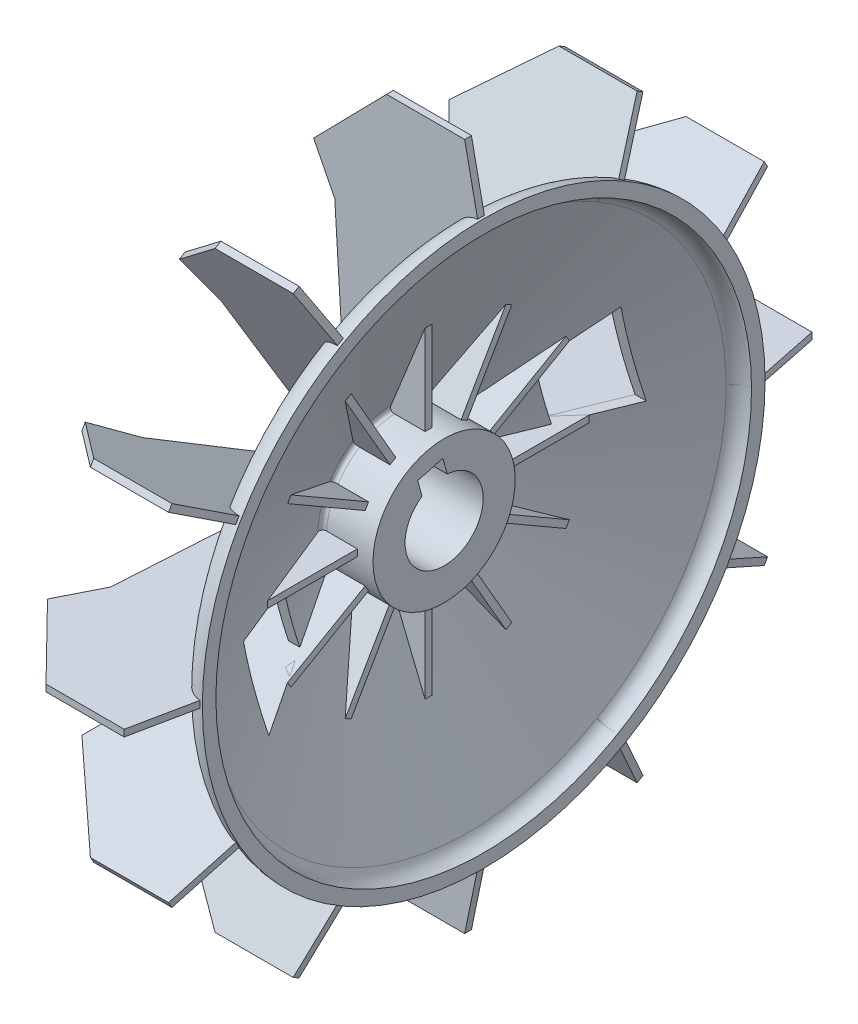
SolidWorks part; units mm, degrees
ref_plane "Plan de face" through (0, 0, 0) normal (0, 0, 1) x (1, 0, 0)
ref_plane "Plan de dessus" through (0, 0, 0) normal (0, 1, 0) x (1, 0, 0)
ref_plane "Plan de droite" through (0, 0, 0) normal (1, 0, 0) x (0, 0, -1)
sketch "Esquisse1" plane through (0, 0, 0) normal (0, 0, 1) x (1, 0, 0)
  line L0 (-19.7316, 0) -> (54.854, 0) construction
  line L1 (0, 7.5) -> (0, 13.65)
  line L2 (0, 13.65) -> (6.1585, 13.65)
  line L3 (20, 13.65) -> (20, 7.5)
  line L4 (20, 7.5) -> (0, 7.5)
  line L5 (8.4746, 15.209) -> (22.9677, 50.882)
  line L6 (27.6, 54) -> (27.6, 51.4)
  line L7 (10.4194, 14.6823) -> (24.5808, 49.5388)
  line L8 (11.1142, 13.65) -> (20, 13.65)
  arc A0 (22.9677, 50.882) -> (27.6, 54) centre (27.6, 49) cw
  arc A1 (24.5808, 49.5388) -> (27.6, 51.4) centre (27.3601, 48.4096) cw
  arc A2 (6.1585, 13.65) -> (8.4746, 15.209) centre (6.1585, 16.15) ccw
  arc A3 (10.4194, 14.6823) -> (11.1142, 13.65) centre (11.1142, 14.4) ccw
  dimension "D3" = 5
  dimension "D7" = 2
  dimension "D8" = 3
  dimension "D10" = 5
  dimension "D11" = 1.5
  dimension "D1" = 2.6
  dimension "D2" = 15
  dimension "D4" = 108
  dimension "D5" = 27.3
  dimension "D6" = 20
  dimension "D9" = 27.6
  dimension "D12" = 8.8858
revolve "Révolution1" add sketch "Esquisse1" angle 360 about L0
sketch "Esquisse2" plane through (0, 0, 0) normal (0, 0, 1) x (1, 0, 0)
  line L0 (1.5, 13.65) -> (-0.3371, 43.6864)
  line L1 (0, 13.65) -> (6.1585, 13.65) construction
  line L2 (-0.3371, 43.6864) -> (-4.4, 51.7171)
  line L3 (-4.4, 51.7171) -> (9.6, 66)
  line L4 (9.6, 66) -> (24.6, 66)
  line L5 (-19.7316, 0) -> (54.854, 0) construction
  line L6 (24.6, 66) -> (27.6, 51.4)
  line L7 (10.4194, 14.6823) -> (24.5808, 49.5388) construction
  line L8 (24.5808, 49.5388) -> (17, 30.8797)
  line L9 (17, 13.65) -> (17, 30.8797)
  line L10 (27.6, -54) -> (27.6, 54) construction
  line L11 (0, 7.5) -> (0, 13.65) construction
  line L12 (8.4746, 15.209) -> (22.9677, 50.882) construction
  line L13 (11.1142, 13.65) -> (20, 13.65) construction
  line L14 (17, 13.65) -> (1.5, 13.65)
  arc A0 (27.6, 51.4) -> (24.5808, 49.5388) centre (27.3601, 48.4096) ccw
  dimension "D1" = 3
  dimension "D2" = 15
  dimension "D3" = 20
  dimension "D4" = 9
  dimension "D5" = 66
  dimension "D6" = 32
  dimension "D7" = 1.5
  dimension "D8" = 3.5
  dimension "D9" = 3
extrude "Extrusion4" add sketch "Esquisse2" along normal blind 0.65 and the other way blind 0.65 separate body
pattern_circular "Répétition circulaire4" count 12 over 360 about axis through (-19.7316, 0, 0) along (1, 0, 0) of bodies 102
sketch "Esquisse3" plane through (27.6, 0, 0) normal (1, 0, 0) x (0, 0, -1)
  line L0 (0, 0) -> (-18.059, 67.3973) construction
  line L1 (-25.1371, 44.8387) -> (-32.4371, 57.4827) construction
  line L4 (-5.0548, 9.2054) -> (-0.2251, 10.4995)
  line L5 (-0.2251, 10.4995) -> (0.5847, 7.4772)
  line L6 (-5.0548, 9.2054) -> (-4.2449, 6.1831)
  line L7 (-4.2449, 6.1831) -> (0.5847, 7.4772)
  line L8 (-69.0447, -18.5005) -> (61.4604, 16.4683) construction
  line L9 (-25.7077, -0.65) -> (-22.5886, -12.291)
  line L10 (-13.65, -0.65) -> (-30.8797, -0.65) construction
  line L11 (-12.1462, -6.2621) -> (-27.0676, -14.8769) construction
  line L12 (-22.5886, -12.291) -> (-33.7957, -18.7614)
  line L14 (-38.6487, -0.65) -> (-25.7077, -0.65)
  line L15 (-38.6487, -0.65) -> (-33.7957, -18.7614)
  line L16 (33.7957, 18.7614) -> (38.6487, 0.65)
  line L17 (33.7957, 18.7614) -> (22.5886, 12.291)
  line L18 (25.7077, 0.65) -> (38.6487, 0.65)
  line L19 (22.5886, 12.291) -> (25.7077, 0.65)
  circle A0 centre (0, 0) radius 7.5 construction
  dimension "D1" = 15
  dimension "D2" = 5
  dimension "D3" = 10.2
  dimension "D4" = 37.5
  dimension "D5" = 25
extrude "Enlèv. mat.-Extru.1" cut sketch "Esquisse3" against normal through all
